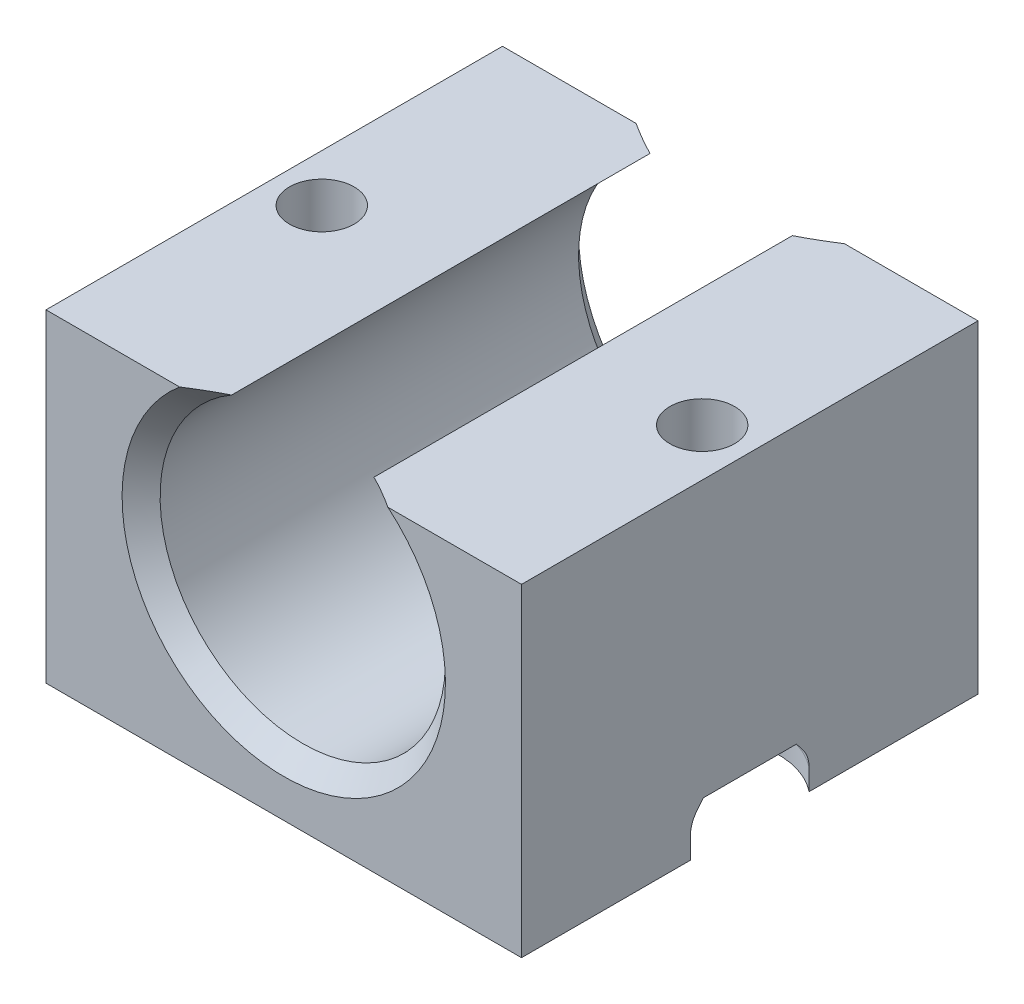
SolidWorks part; units mm, degrees
material "ABS PC"
ref_plane "Front Plane" through (0, 0, 0) normal (0, 0, 1) x (1, 0, 0)
ref_plane "Top Plane" through (0, 0, 0) normal (0, 1, 0) x (1, 0, 0)
ref_plane "Right Plane" through (0, 0, 0) normal (1, 0, 0) x (0, 0, -1)
sketch "Sketch1" plane through (0, 0, 0) normal (0, 1, 0) x (1, 0, 0)
  line L0 (0, 0) -> (0, 24)
  line L1 (0, 0) -> (25, 0)
  line L2 (0, 24) -> (25, 24)
  line L3 (25, 0) -> (25, 24)
  dimension "D1" = 24
  dimension "D2" = 25
extrude "Boss-Extrude1" add sketch "Sketch1" along normal blind 17
sketch "Sketch2" plane through (0, 0, 0) normal (0, 0, 1) x (1, 0, 0)
  line L0 (0, 17) -> (25, 17) construction
  line L1 (0, 0) -> (25, 0) construction
  line L2 (0, 17) -> (0, 0) construction
  arc A0 (8.7583, 17) -> (16.2417, 17) centre (12.5, 10.5) ccw
  dimension "D1" = 7.5
  dimension "D2" = 10.5
  dimension "D3" = 12.5
extrude "Cut-Extrude1" cut sketch "Sketch2" against normal through all and the other way through all
hole_wizard "Ø3.4 (3.4) Diameter Hole1" positions "Sketch4" profile "Sketch3" hole size "Ø3.4" standard "ANSI Metric" end condition through all
sketch "Sketch4" plane through (0, 17, 0) normal (0, 1, 0) x (1, 0, 0)
  line L0 (8.7583, 24) -> (0, 24) construction
  line L1 (0, 24) -> (0, 0) construction
  line L2 (25, 0) -> (25, 24) construction
  point P0 (22.5, 12)
  point P2 (2.5, 12)
  dimension "D1" = 12
  dimension "D2" = 2.5
  dimension "D3" = 2.5
sketch "Sketch3" plane through (22.5, 17, -12) normal (1, 0, 0) x (0, 0, 1)
  line L0 (0, 0) -> (0, 17)
  line L1 (0, 17) -> (1.7, 17)
  line L2 (1.7, 17) -> (1.7, 0)
  line L5 (1.7, 0) -> (0, 0)
  line L11 (0, -6.35) -> (0, 107.95) construction
  dimension "Thru Hole Dia." = 3.4
  dimension "Thru Hole Depth" = 17
sketch "Sketch5" plane through (0, 0, 0) normal (0, -1, 0) x (1, 0, 0)
  circle A0 centre (2.5, -12) radius 4
  circle A1 centre (22.5, -12) radius 4
  dimension "D1" = 8
extrude "Cut-Extrude2" cut sketch "Sketch5" against normal blind 2.5
chamfer "Chamfer1" distance 1 angle 45 2 edges at (12.5, 3, -24) (12.5, 3, 0)
chamfer "Chamfer2" distance 0.5 angle 60 2 edges at (6.5, 2.5, -12) (18.5, 2.5, -12) first distance on face at (2.5, 2.5, -13.7) first distance on face at (22.5, 2.5, -13.7)
fillet "Fillet1" radius 2 2 edges at (6.5, 1.634, -12) (18.5, 1.634, -12)
